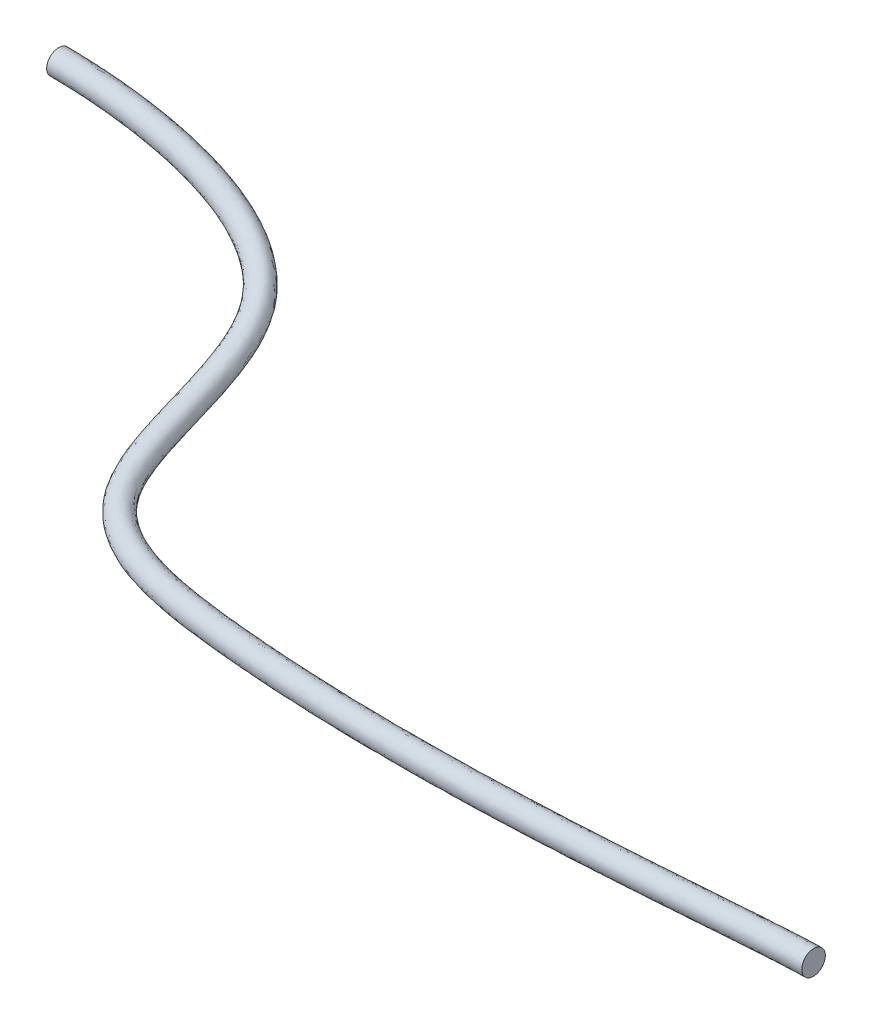
SolidWorks part; units mm, degrees
ref_plane "Front Plane" through (0, 0, 0) normal (0, 0, 1) x (1, 0, 0)
ref_plane "Top Plane" through (0, 0, 0) normal (0, 1, 0) x (1, 0, 0)
ref_plane "Right Plane" through (0, 0, 0) normal (1, 0, 0) x (0, 0, -1)
ref_plane "Plane1" through (0, 40.894, 0) normal (0, 1, 0) x (1, 0, 0)
ref_plane "Plane2" through (0, 3.5, 0) normal (0, 1, 0) x (1, 0, 0)
sketch3d "3DSketch1"
  line L0 (0, 0, 83) -> (129.2022, 0, 83) construction
  line L1 (300, 3.5, 80) -> (129.2022, 3.5, 83) construction
  line L2 (0, 0, 0) -> (0, 0, 80) construction
  line L3 (0, 0, 80) -> (300, 0, 80) construction
  line L4 (-28.7931, 40.894, 0) -> (16.0619, 40.894, 0) construction
  line L5 (41.4808, 3.5, 73.3203) -> (202.8603, 3.5, 91.1279) construction
  spline S0 degree 3 poles (0, 40.894, 0) (16.5033, 40.894, 0) (92.6369, 30.7375, -4.7989) (70.7793, 3.5, 73.4271) (175.7011, 3.5, 93.418) (274.658, 3.5, 80.4451) (300, 3.5, 80) knots 0 0 0 0 0.228579 0.377464 0.515223 1 1 1 1
  point P0 (0, 40.894, 0)
  point P1 (74.9199, 25, 16.9639)
  point P3 (84.106, 7, 65.3791)
  point P4 (300, 3.5, 80)
  point P6 (47.0864, 35, 2.2366)
  point P7 (129.2022, 3.5, 83)
  point P9 (0, 40.894, 0)
  point P18 (84.106, 7, 65.3791)
  point P26 (0, 0, 0)
  point P27 (0, 0, 0)
  point P28 (0, 40.894, 0)
  point P29 (0, 40.894, 0)
  dimension "D1" = 80
  dimension "D2" = 300
  dimension "D3" = 35
  dimension "D4" = 25
  dimension "D5" = 7
  dimension "D6" = 83
sketch "Sketch2" plane through (0, 0, 0) normal (1, 0, 0) x (0, 0, -1)
  circle A0 centre (0, 40.894) radius 3.5
  point P2 (0, 0)
  point P3 (0, 0)
  dimension "D1" = 7
sweep "Sweep1" add profiles "Sketch2" path "3DSketch1"
